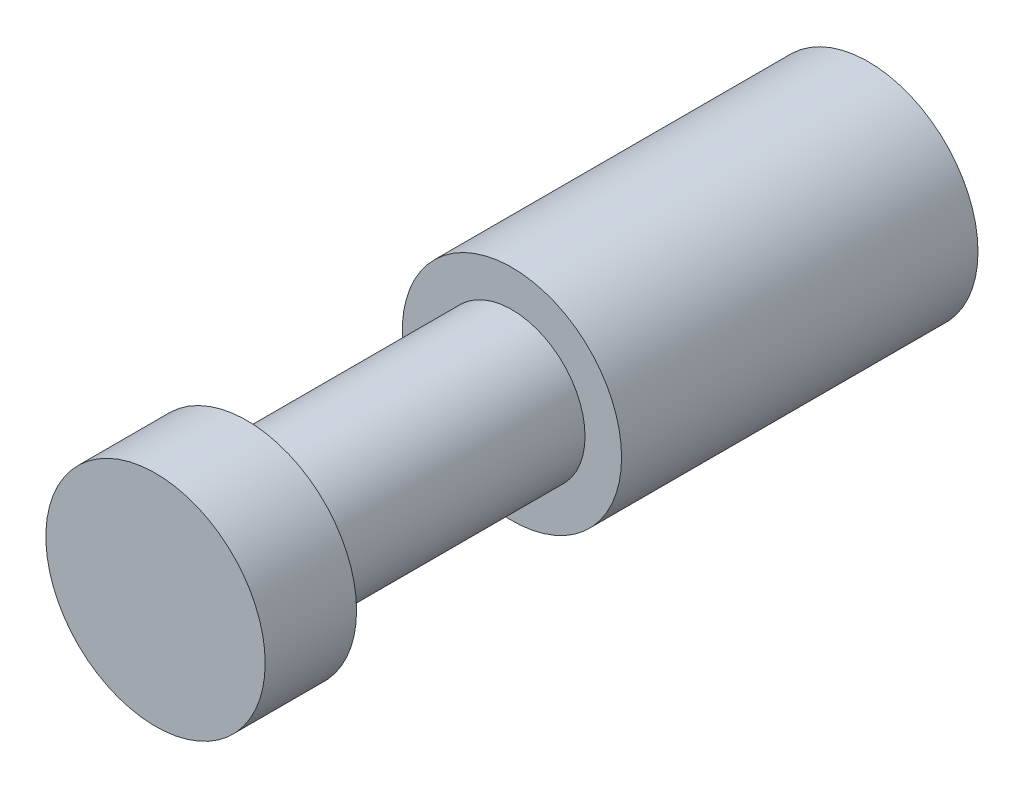
SolidWorks part; units mm, degrees
ref_plane "Front Plane" through (0, 0, 0) normal (0, 0, 1) x (1, 0, 0)
ref_plane "Top Plane" through (0, 0, 0) normal (0, 1, 0) x (1, 0, 0)
ref_plane "Right Plane" through (0, 0, 0) normal (1, 0, 0) x (0, 0, -1)
sketch "Sketch1" plane through (0, 0, 0) normal (0, 0, 1) x (1, 0, 0)
  circle A0 centre (0, 0) radius 4.2
  circle A1 centre (0, 0) radius 6
  dimension "D1" = 8.4
  dimension "D2" = 12
extrude "Boss-Extrude1" add sketch "Sketch1" along normal blind 12
sketch "Sketch2" plane through (0, 0, 12) normal (0, 0, 1) x (1, 0, 0)
  circle A0 centre (0, 0) radius 6
  circle A1 centre (0, 0) radius 6 construction
  dimension "D1" = 0
extrude "Boss-Extrude2" add sketch "Sketch2" along normal blind 2
sketch "Sketch3" plane through (0, 0, 14) normal (0, 0, 1) x (1, 0, 0)
  circle A0 centre (0, 0) radius 4
  dimension "D1" = 8
extrude "Boss-Extrude3" add sketch "Sketch3" along normal blind 20
sketch "Sketch4" plane through (0, 0, 34) normal (0, 0, 1) x (1, 0, 0)
  circle A0 centre (0, 0) radius 6
  dimension "D1" = 12
extrude "Boss-Extrude4" add sketch "Sketch4" along normal blind 5
sketch "Sketch5" plane through (0, 0, 14) normal (0, 0, 1) x (1, 0, 0)
  circle A0 centre (0, 0) radius 6
  circle A1 centre (0, 0) radius 6 construction
extrude "Boss-Extrude5" add sketch "Sketch5" along normal blind 5.5
